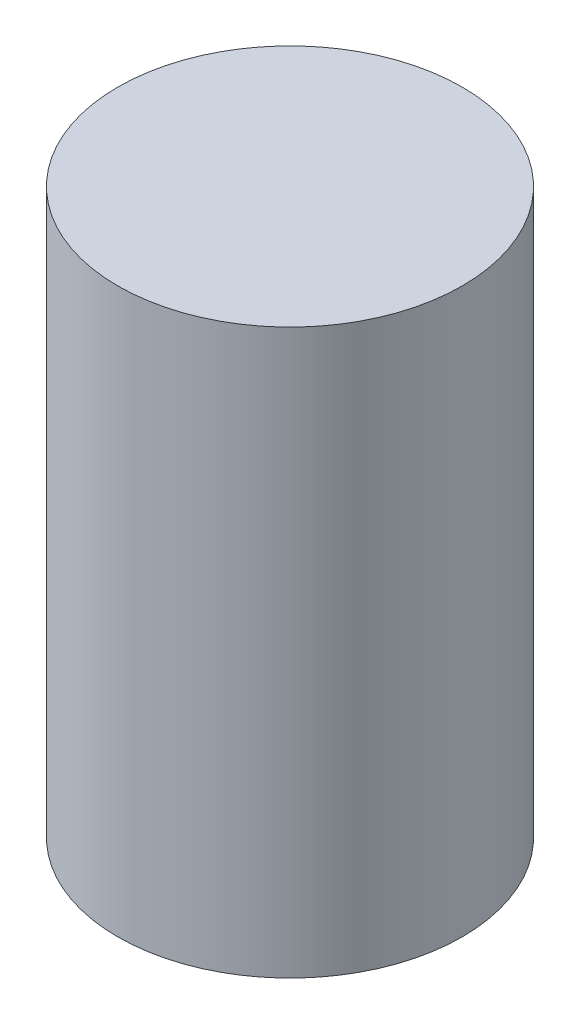
SolidWorks part; units mm, degrees
ref_plane "X-Y Datum" through (0, 0, 0) normal (0, 0, 1) x (1, 0, 0)
ref_plane "X-Z Datum" through (0, 0, 0) normal (0, 1, 0) x (1, 0, 0)
ref_plane "Y-Z Datum" through (0, 0, 0) normal (1, 0, 0) x (0, 0, -1)
sketch3d "3DSketch1"
  line L0 (266.6111, -155.9767, 163.3218) -> (266.6111, -140.5937, 163.3218)
  circle A0 centre (266.6111, -140.5937, 163.3218) radius 3.95 construction
  circle A1 centre (266.6111, -155.9767, 163.3218) radius 3.95 construction
  point P0 (266.6111, -140.5937, 163.3218)
  point P1 (266.6111, -155.9767, 163.3218)
  point P4 (266.6111, -136.6437, 163.3218)
  point P8 (266.6111, -159.9267, 163.3218)
sweep "Sweep1" add path "3DSketch1" circular profile diameter 9.398 parameters "D3"=9.398
